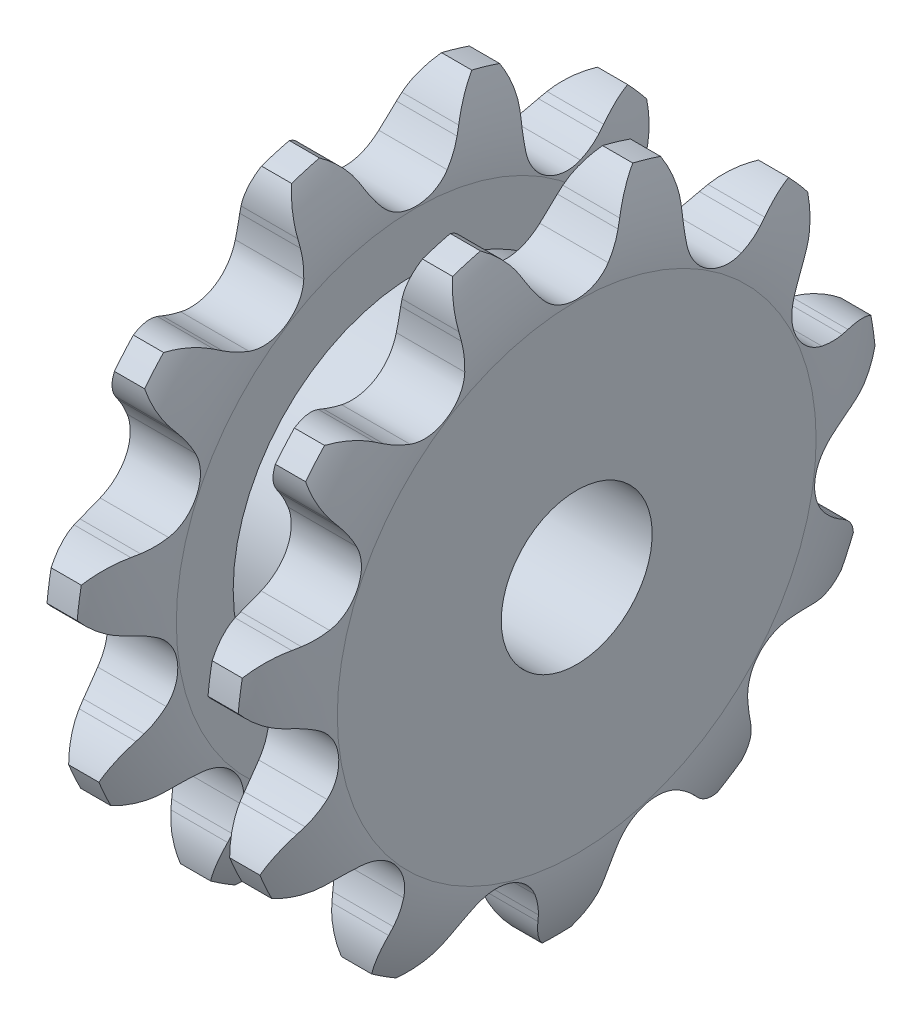
SolidWorks part; units mm, degrees
ref_plane "Plane1" through (0, 0, 0) normal (0, 0, 1) x (1, 0, 0)
ref_plane "Plane2" through (0, 0, 0) normal (0, 1, 0) x (1, 0, 0)
ref_plane "Plane3" through (0, 0, 0) normal (1, 0, 0) x (0, 0, -1)
sketch "Clipboard" plane through (0, 0, 0) normal (0, 1, 0) x (1, 0, 0)
  line L0 (0, 0) -> (6.2333, -1.2116)
  line L1 (-15, 0) -> (100, 0) construction
  line L2 (0, 0) -> (-0.5301, 0.5991)
  line L3 (0, 0) -> (-2.9891, 1.1425)
  line L4 (0, 0) -> (3.043, 0.5915)
  line L5 (0, 0) -> (-89.0105, -33.1983)
  line L6 (0, 0) -> (-7.6265, -5.1456)
  line L7 (-0.5301, 0.5991) -> (92.0355, 21.9696)
  line L8 (-76.2, 38.1) -> (-75.2, 38.1)
  line L9 (-73.2358, 39.4872) -> (-73.0836, 39.4947)
  line L10 (-73.0533, 76.1892) -> (-66.6533, 76.1892)
  circle A0 centre (0, 0) radius 1.651
  circle A1 centre (0, 0) radius 4
  circle A2 centre (0, 0) radius 4
  dimension "Num_teeth" = 11
  dimension "Thickness" = 9.2
sketch "BasProSke" plane through (0, 0, 0) normal (0, 1, 0) x (1, 0, 0)
  line L0 (-10, 0) -> (60, 0) construction
  line L1 (0, 0) -> (0, 9.5181)
  line L2 (0, 0) -> (9.2, 0)
  line L3 (9.2, 0) -> (9.2, 9.5181)
  line L4 (8.4, 12.7181) -> (0.8, 12.7181)
  arc A0 (0, 9.5181) -> (0.8, 12.7181) centre (6.8, 9.5181) cw
  arc A1 (9.2, 9.5181) -> (8.4, 12.7181) centre (2.4, 9.5181) ccw
  dimension "D1" = 6.8
  dimension "Thickness" = 9.2
  dimension "Diameter" = 25.4361
  dimension "H1" = 3.2
  dimension "G1" = 0.8
revolve "Base-Revolve" add sketch "BasProSke" angle 360 about L0
sketch "GrvSke" plane through (0, 0, 0) normal (0, 1, 0) x (1, 0, 0)
  line L0 (2.8, 9.5181) -> (2.8, 7.2571)
  line L1 (2.8, 7.2571) -> (6.4, 7.2571)
  line L2 (6.4, 7.2571) -> (6.4, 9.5181)
  line L3 (2, 12.7181) -> (7.2, 12.7181)
  line L4 (4.6, 0) -> (4.6, 52.07) construction
  line L5 (-10, 0) -> (60, 0) construction
  line L6 (0, 0) -> (35.56, 0) construction
  arc A0 (6.4, 9.5181) -> (7.2, 12.7181) centre (13.2, 9.5181) cw
  arc A1 (2.8, 9.5181) -> (2, 12.7181) centre (-4, 9.5181) ccw
  dimension "Diameter" = 25.4361
  dimension "H1" = 3.2
  dimension "G1" = 0.8
revolve "Groove" cut sketch "GrvSke" angle 360 about L6
pattern_linear "Grooves" [suppressed]
sketch "TooCutSke" plane through (0, 0, 0) normal (1, 0, 0) x (0, 0, -1)
  line L0 (1.8371, 10.977) -> (1.9787, 11.2486)
  line L1 (0, 0) -> (0, 107) construction
  line L2 (0, 11.2696) -> (-10, 11.2696) construction
  line L3 (-1.8371, 10.977) -> (-1.9787, 11.2486)
  arc A0 (1.2916, 10.1682) -> (1.8371, 10.977) centre (-2.01, 12.9835) ccw
  arc A1 (1.2916, 10.1682) -> (-1.2916, 10.1682) centre (0, 11.2696) cw
  arc A2 (1.9787, 11.2486) -> (4.4355, 12.7381) centre (4.4355, 9.9672) cw
  arc A3 (-1.2916, 10.1682) -> (-1.8371, 10.977) centre (2.01, 12.9835) cw
  arc A4 (-1.9787, 11.2486) -> (-4.4355, 12.7381) centre (-4.4355, 9.9672) ccw
  arc A5 (4.4355, 12.7381) -> (-4.4355, 12.7381) centre (0, 0) ccw
  dimension "Pitch_radius" = 11.2696
  dimension "V" = 1.3024
extrude "ToothCut" cut sketch "TooCutSke" along normal through all
pattern_circular "TeethCuts" count 11 every 32.727 about axis through (-10, 0, 0) along (1, 0, 0) of "ToothCut"
sketch "HubNeaOneSke" plane through (0, 0, 0) normal (-1, 0, 0) x (0, 0, 1)
  circle A0 centre (0, 0) radius 4
  dimension "Diameter" = 8
extrude "HubNearOne" [suppressed] add sketch "HubNeaOneSke" along normal blind 85.8005
sketch "HubNeaBotSke" plane through (0, 0, 0) normal (-1, 0, 0) x (0, 0, 1)
  circle A0 centre (0, 0) radius 4
  dimension "Diameter" = 8
extrude "HubNearBoth" [suppressed] add sketch "HubNeaBotSke" along normal blind 42.9002
ref_plane "FarPln" through (9.2, 0, 0) normal (1, 0, 0) x (0, 0, -1)
sketch "HubFarSke" plane through (9.2, 0, 0) normal (1, 0, 0) x (0, 0, -1)
  circle A0 centre (0, 0) radius 4
  dimension "Diameter" = 8
extrude "HubFar" [suppressed] add sketch "HubFarSke" along normal blind 42.9002
sketch "BorSke" plane through (0, 0, 0) normal (1, 0, 0) x (0, 0, -1)
  circle A0 centre (0, 0) radius 3
  dimension "Diameter" = 6
extrude "Bore" cut sketch "BorSke" along normal mid plane 190.001
sketch "KeySke" plane through (0, 0, 0) normal (1, 0, 0) x (0, 0, -1)
  line L0 (-1, 0) -> (-1, 4)
  line L1 (-1, 4) -> (1, 4)
  line L2 (1, 4) -> (1, 0)
  line L3 (0, 0) -> (0, 34) construction
  line L4 (-1, 0) -> (1, 0)
  dimension "Offset" = 4
  dimension "Width" = 2
extrude "Keyway" [suppressed] cut sketch "KeySke" along normal mid plane 190.001
pattern_circular "Keyway2" [suppressed] count 2 every 90 about axis through (-10, 0, 0) along (1, 0, 0)
equation "' \"Pitch@Clipboard\" = 6.35"
equation "' \"Num_strands@Clipboard\" = 2"
equation "' \"Num_teeth@Clipboard\" = 11"
equation "' \"Hub_dia@Clipboard\" = 8"
equation "' \"Overall_len@Clipboard\" = 95"
equation "' \"Diameter@BorSke\" = 6"
equation "' \"T_dim@Clipboard\" = 1"
equation "' \"Width@KeySke\" = 2"
equation "' \"Dr@Clipboard\" = 3.302"
equation "' \"Face_width@Clipboard\" = 2.8"
equation "' \"Chamfer_dep@Clipboard\" = 3.2"
equation "' \"Chamfer_wid@Clipboard\" = 0.8"
equation "' \"Transv_pitch@Clipboard\" = 6.4"
equation "' \"Show_teeth@Clipboard\" = 11"
equation "\"Num_teeth@Clipboard\" = int( \"Num_teeth@Clipboard\" )"
equation "\"Num_teeth@Clipboard\" = ((sgn( \"Num_teeth@Clipboard\" - 5.0)+1)*( \"Num_teeth@Clipboard\" - 5.0))/2 +5.0"
equation "\"Num_teeth@Clipboard\" = ((sgn( \"Num_teeth@Clipboard\" - 200.0)-1)*( \"Num_teeth@Clipboard\" - 200.0))/-2 +200.0"
equation "\"MHD@Clipboard\" = \"Pitch@Clipboard\" * (1.0 / tan(3.14159265 / \"Num_teeth@Clipboard\" ) - 1.0) - 0.762"
equation "\"Thickness@Clipboard\"  = \"Face_width@Clipboard\" + (\"Num_strands@Clipboard\" - 1) * \"Transv_pitch@Clipboard\""
equation "\"OAL@Clipboard\" = \"Thickness@Clipboard\""
equation "\"MHD@Clipboard\" = ((sgn( \"MHD@Clipboard\" - \"Hub_dia@Clipboard\" )-1)*( \"MHD@Clipboard\" - \"Hub_dia@Clipboard\" ))/-2+ \"Hub_dia@Clipboard\""
equation "\"OAL@Clipboard\" = ((sgn( \"OAL@Clipboard\" - \"Overall_len@Clipboard\" )+1)*( \"OAL@Clipboard\" - \"Overall_len@Clipboard\" ))/2 + \"Overall_len@Clipboard\" + 0.0005"
equation "\"Num_teeth@TeethCuts\" = int( \"Show_teeth@Clipboard\" ) + 1"
equation "\"Num_teeth@TeethCuts\" = ((sgn( \"Num_teeth@TeethCuts\" - \"Num_teeth@Clipboard\" )-1)*( \"Num_teeth@TeethCuts\" - \"Num_teeth@Clipboard\" ))/-2+ \"Num_teeth@Clipboard\""
equation "\"Num_teeth@TeethCuts\" = ((sgn( \"Num_teeth@TeethCuts\" - 2.0)+1)*( \"Num_teeth@TeethCuts\" - 2.0))/2 +2.0"
equation "\"Angle@TeethCuts\" = 360.0 / \"Num_teeth@Clipboard\""
equation "\"Pitch_radius@TooCutSke\" = ( \"Pitch@Clipboard\" / 2.0) / sin(3.14159265 / \"Num_teeth@Clipboard\" )  'ma"
equation "\"R@TooCutSke\"  = \"Dr@Clipboard\" * 0.5025 + 0.0381"
equation "\"A@TooCutSke\" = 35.0 + (60.0 / \"Num_teeth@Clipboard\")"
equation "\"E@TooCutSke\"  = \"Dr@Clipboard\" * 1.3025 + 0.0381"
equation "\"B@TooCutSke\"  = 18.0 - (56.0 / \"Num_teeth@Clipboard\" )"
equation "\"W@TooCutSke\" = 1.4 * \"Dr@Clipboard\" * cos(3.14159265 / \"Num_teeth@Clipboard\" )"
equation "\"V@TooCutSke\" = 1.4 * \"Dr@Clipboard\" * sin(3.14159265 / \"Num_teeth@Clipboard\" )"
equation "\"Diameter@BasProSke\" = 2.0 * ( (0.3 * \"Pitch@Clipboard\" ) +  \"Pitch@Clipboard\" / 2.0 / tan(3.14159265 / \"Num_teeth@Clipboard\" ))"
equation "\"Thickness@BasProSke\"  = \"Thickness@Clipboard\""
equation "\"G1@BasProSke\" =  \"Chamfer_wid@Clipboard\""
equation "\"G2@BasProSke\" =  \"Chamfer_wid@Clipboard\""
equation "\"H1@BasProSke\" =  \"Chamfer_dep@Clipboard\""
equation "\"H2@BasProSke\" =  \"Chamfer_dep@Clipboard\""
equation "\"Diameter@GrvSke\" = \"Diameter@BasProSke\""
equation "\"G1@GrvSke\" = \"Chamfer_wid@Clipboard\""
equation "\"H1@GrvSke\" = \"Chamfer_dep@Clipboard\""
equation "\"Grv_diam@GrvSke\" =  \"Pitch@Clipboard\" * (1.0 / tan(3.14159265 / \"Num_teeth@Clipboard\" ) - 1.0) - 0.762"
equation "\"Grv_width@GrvSke\" =  \"Transv_pitch@Clipboard\" - \"Face_width@Clipboard\""
equation "\"Offset@GrvSke\" = \"Grv_width@GrvSke\" / 2.0 + \"Face_width@Clipboard\""
equation "\"Offset@Grooves\" = \"Transv_pitch@Clipboard\""
equation "\"Num_grvs@Grooves\" = \"Num_strands@Clipboard\""
equation "\"Num_grvs@Grooves\" = \"Num_grvs@Grooves\" - 1 * sgn( \"Num_grvs@Grooves\" -1)"
equation "\"Diameter@HubNeaOneSke\" = \"MHD@Clipboard\""
equation "\"Length@HubNearOne\" = \"OAL@Clipboard\" - \"Thickness@BasProSke\""
equation "\"Diameter@HubNeaBotSke\" = \"MHD@Clipboard\""
equation "\"Length@HubNearBoth\" = ( \"OAL@Clipboard\" - \"Thickness@BasProSke\" ) / 2.0"
equation "\"Thickness@FarPln\" = \"Thickness@BasProSke\""
equation "\"Diameter@HubFarSke\" = \"MHD@Clipboard\""
equation "\"Length@HubFar\" = ( \"OAL@Clipboard\" - \"Thickness@BasProSke\" ) / 2.0"
equation "\"D1@Bore\" = \"OAL@Clipboard\" * 2.0"
equation "\"D1@Keyway\" = \"OAL@Clipboard\" * 2.0"
equation "\"Offset@KeySke\" = \"T_dim@Clipboard\" + \"Diameter@BorSke\" / 2.0"
